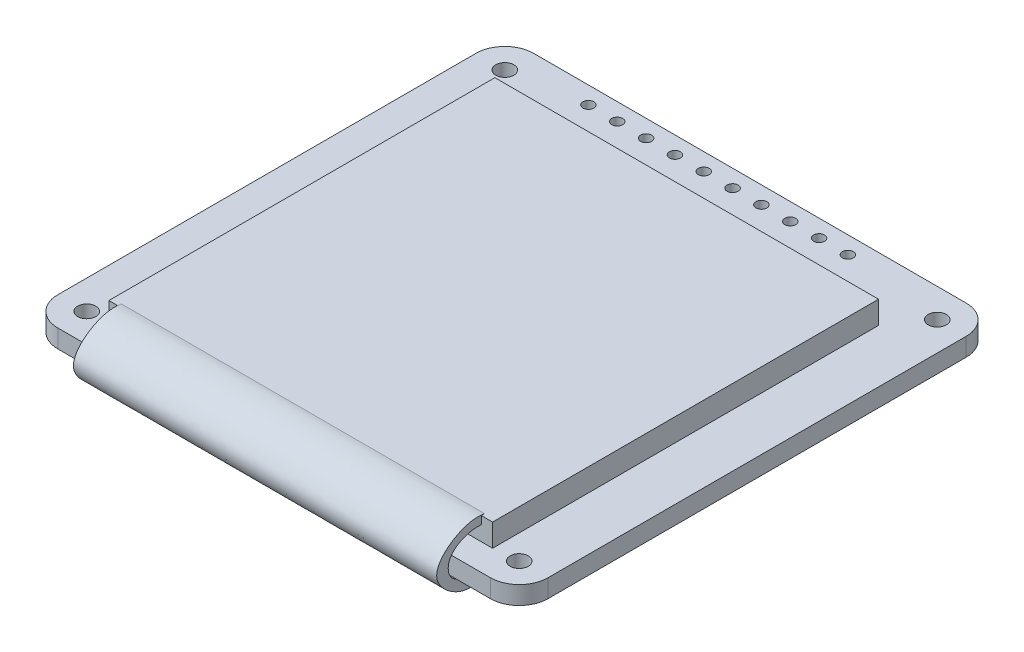
SolidWorks part; units mm, degrees
ref_plane "Front Plane" through (0, 0, 0) normal (0, 0, 1) x (1, 0, 0)
ref_plane "Top Plane" through (0, 0, 0) normal (0, 1, 0) x (1, 0, 0)
ref_plane "Right Plane" through (0, 0, 0) normal (1, 0, 0) x (0, 0, -1)
sketch "Sketch1" plane through (0, 0, 0) normal (0, 1, 0) x (1, 0, 0)
  line L0 (0, 39.37) -> (0, 2.54)
  line L1 (2.54, 0) -> (40.64, 0)
  line L2 (43.18, 2.54) -> (43.18, 39.37)
  line L3 (40.64, 41.91) -> (2.54, 41.91)
  arc A0 (0, 2.54) -> (2.54, 0) centre (2.54, 2.54) ccw
  arc A1 (40.64, 0) -> (43.18, 2.54) centre (40.64, 2.54) ccw
  arc A2 (43.18, 39.37) -> (40.64, 41.91) centre (40.64, 39.37) ccw
  arc A3 (2.54, 41.91) -> (0, 39.37) centre (2.54, 39.37) ccw
  circle A4 centre (31.75, 40.386) radius 0.4826
  circle A5 centre (31.75, 40.386) radius 0.4826
  circle A6 centre (29.21, 40.386) radius 0.4826
  circle A7 centre (29.21, 40.386) radius 0.4826
  circle A8 centre (26.67, 40.386) radius 0.4826
  circle A9 centre (26.67, 40.386) radius 0.4826
  circle A10 centre (24.13, 40.386) radius 0.4826
  circle A11 centre (24.13, 40.386) radius 0.4826
  circle A12 centre (21.59, 40.386) radius 0.4826
  circle A13 centre (21.59, 40.386) radius 0.4826
  circle A14 centre (19.05, 40.386) radius 0.4826
  circle A15 centre (19.05, 40.386) radius 0.4826
  circle A16 centre (16.51, 40.386) radius 0.4826
  circle A17 centre (16.51, 40.386) radius 0.4826
  circle A18 centre (13.97, 40.386) radius 0.4826
  circle A19 centre (13.97, 40.386) radius 0.4826
  circle A20 centre (11.43, 40.386) radius 0.4826
  circle A21 centre (11.43, 40.386) radius 0.4826
  circle A22 centre (8.89, 40.386) radius 0.4826
  circle A23 centre (8.89, 40.386) radius 0.4826
  circle A24 centre (2.54, 2.54) radius 0.8
  circle A25 centre (2.54, 2.54) radius 0.8
  circle A26 centre (40.64, 2.54) radius 0.8
  circle A27 centre (40.64, 2.54) radius 0.8
  circle A28 centre (40.64, 39.37) radius 0.8
  circle A29 centre (40.64, 39.37) radius 0.8
  circle A30 centre (2.54, 39.37) radius 0.8
  circle A31 centre (2.54, 39.37) radius 0.8
extrude "Boss-Extrude1" add sketch "Sketch1" along normal blind 1.6 contours L3 A3 L0 A0 L1 A1 L2 A2 A30 A28 A26 A24 A22 A20 A18 A16 A14 A12 A10 A8 A6 A4 region at (21.5952, 0, -20.8755)
sketch "Sketch2" plane through (0, 1.6, 0) normal (0, 1, 0) x (1, 0, 0)
  line L0 (0, 39.37) -> (0, 2.54) construction
  line L1 (4.69, 36.3438) -> (38.49, 36.3438)
  line L2 (4.69, 36.3438) -> (4.69, 2.3438)
  line L3 (4.69, 2.3438) -> (38.49, 2.3438)
  line L4 (38.49, 36.3438) -> (38.49, 2.3438)
  line L5 (43.18, 2.54) -> (43.18, 39.37) construction
  dimension "D1" = 33.8
  dimension "D2" = 34
  dimension "D3" = 4.69
  dimension "D4" = 4.69
extrude "Boss-Extrude2" add sketch "Sketch2" along normal blind 2
sketch "Sketch3" plane through (0, 0, 0) normal (1, 0, 0) x (0, 0, -1)
  spline S0 degree 3 poles (8.2816, -0.2295) (4.1539, 3.3516) (1.0034, 4.0569) (-2.8961, 1.1671) (0.1, -1.4379) (2.9832, -1.4241) (8.2816, -0.2295) (4.1539, 3.3516) (1.0034, 4.0569) knots -0.504023 -0.428158 -0.185343 0 0.142118 0.339134 0.495977 0.571842 0.814657 1 1.142118 1.339134 1.495977 only from (3.9702, 3.1053) to (3.9702, 3.1053)
  spline S1 degree 3 poles (5.1576, 1.2954) (3.6929, 2.6724) (1.536, 3.293) (-0.8599, 1.8627) (-0.4616, 0.1711) (1.129, -0.6658) (3.1681, -0.4896) (4.995, 0.0056) (5.1576, 1.2954) (3.6929, 2.6724) (1.536, 3.293) knots -0.252278 -0.209355 -0.084678 0 0.200569 0.386571 0.476144 0.515166 0.747722 0.790645 0.915322 1 1.200569 1.386571 1.476144 only from (4.0818, 2.2318) to (4.0818, 2.2318)
  point P2 (-0.0919, 0)
  point P4 (4.4182, -0.1336)
  point P6 (-1.5847, 0.9072)
extrude "Boss-Extrude3" add sketch "Sketch3" along normal blind 32 from offset 5.5
